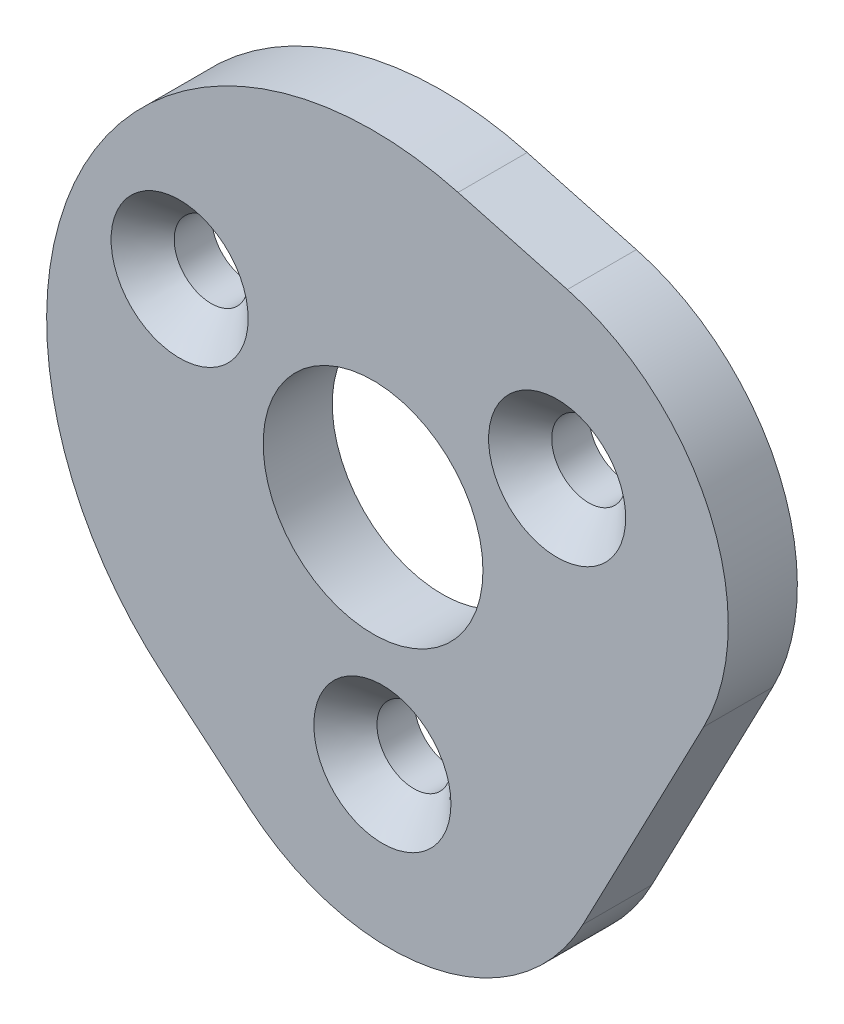
SolidWorks part; units mm, degrees
material "6061-T6 (SS)"
ref_plane "Front Plane" through (0, 0, 0) normal (0, 0, 1) x (1, 0, 0)
ref_plane "Top Plane" through (0, 0, 0) normal (0, 1, 0) x (1, 0, 0)
ref_plane "Right Plane" through (0, 0, 0) normal (1, 0, 0) x (0, 0, -1)
sketch "Sketch1" plane through (0, 0, 0) normal (0, 0, 1) x (1, 0, 0)
  line L0 (-107.4168, -1.9907) -> (-93.8964, -13.3356)
  line L2 (-76.828, 19.386) -> (-93.8964, -13.3356)
  line L3 (-85.3622, 3.0252) -> (-97.775, 9.5) construction
  line L6 (-107.4168, -1.9907) -> (-103.1456, -5.5747)
  line L7 (-83.9149, -16) -> (69.2267, -16)
  line L8 (69.2267, -16) -> (77.4756, -11.2375)
  line L9 (77.4756, -11.2375) -> (61.75, 16)
  line L10 (61.75, 16) -> (-64.275, 16)
  line L11 (-64.275, 16) -> (-72.5616, 18.2352)
  line L12 (-107.4168, -1.9907) -> (-103.1456, -5.5747) construction
  line L17 (-64.275, 16) -> (-72.5616, 18.2352) construction
  line L166 (-125.275, -23) -> (-103.8037, -23)
  line L167 (-125.275, -23) -> (-103.8037, -23)
  line L168 (-99.1549, -21.9694) -> (-88.5637, -17.0306)
  line L169 (-99.1549, -21.9694) -> (-88.5637, -17.0306)
  line L170 (-103.5739, -10.4709) -> (-125.275, -23)
  line L171 (-103.5739, -10.4709) -> (-125.275, -23)
  line L339 (-91.6684, 23.3889) -> (-93.8686, 23.9824)
  line L340 (-91.6684, 23.3889) -> (-93.8686, 23.9824)
  line L351 (-76.828, 19.386) -> (-91.6684, 23.3889)
  circle A0 centre (-97.775, 9.5) radius 5 construction
  circle A1 centre (-97.775, 9.5) radius 5 construction
  arc A2 (-103.8037, -23) -> (-99.1549, -21.9694) centre (-103.8037, -12) ccw
  arc A3 (-93.8686, 23.9824) -> (-107.4168, -1.9907) centre (-97.775, 9.5) ccw
  arc A5 (-93.8686, 23.9824) -> (-107.4168, -1.9907) centre (-97.775, 9.5) ccw
  circle A6 centre (-97.775, 9.5) radius 5.05
  arc A59 (-103.8037, -23) -> (-99.1549, -21.9694) centre (-103.8037, -12) ccw
  arc A60 (-83.9149, -16) -> (-88.5637, -17.0306) centre (-83.9149, -27) ccw
  arc A61 (-83.9149, -16) -> (-88.5637, -17.0306) centre (-83.9149, -27) ccw
  arc A62 (-103.5739, -10.4709) -> (-103.1456, -5.5747) centre (-105.0739, -7.8728) ccw
  arc A63 (-103.5739, -10.4709) -> (-103.1456, -5.5747) centre (-105.0739, -7.8728) ccw
  arc A144 (-74.6395, 20.2232) -> (-72.5616, 18.2352) centre (-71.7803, 21.1317) ccw
  arc A146 (-74.6395, 20.2232) -> (-105.775, 43) centre (-105.775, 10.3307) ccw
  arc A148 (-88.2446, 27.7057) -> (-105.775, 43) centre (-117.312, 12.0824) ccw
  arc A150 (-91.6684, 23.3889) -> (-88.2446, 27.7057) centre (-90.8871, 26.2854) ccw
  dimension "D3" = 10.1
  dimension "D2" = 14
  dimension "D1" = 0
extrude "Boss-Extrude1" add sketch "Sketch1" along normal blind 3.175 contours A5 L0 L2 A6 region at (-110.6117, 16.1959, 0)
fillet "Fillet1" radius 10 2 edges at (-93.8964, -13.3356, 1.5875) (-76.828, 19.386, 1.5875)
sketch "Sketch2" plane through (0, 0, 3.175) normal (0, 0, 1) x (1, 0, 0)
  line L0 (-102.2525, 11.8356) -> (-111.0744, 16.4373) construction
  circle A1 centre (-97.775, 9.5) radius 5.05 construction
  arc A3 (-93.8686, 23.9824) -> (-107.4168, -1.9907) centre (-97.775, 9.5) ccw construction
  circle A4 centre (-97.775, 9.5) radius 5.05 construction
  arc A5 (-93.8686, 23.9824) -> (-107.4168, -1.9907) centre (-97.775, 9.5) ccw construction
  point P8 (-106.6634, 14.1364)
hole_wizard "CSK for M3 Flat Head Machine Screw1" positions "Sketch3" profile "Sketch4" countersink size "M3" standard "ANSI Metric" end condition through all
sketch "Sketch3" plane through (0, 0, 3.175) normal (0, 0, 1) x (1, 0, 0)
  point P0 (-106.6634, 14.1364)
  point P3 (-106.6634, 14.1364)
sketch "Sketch4" plane through (-106.6634, 14.1364, 3.175) normal (1, 0, 0) x (0, -1, 0)
  line L0 (0, 0) -> (0, 3.175)
  line L1 (0, 3.175) -> (1.7, 3.175)
  line L2 (1.7, 3.175) -> (1.7, 1.45)
  line L3 (1.7, 1.45) -> (3.15, 0)
  line L5 (3.15, 0) -> (0, 0)
  line L6 (-1.7, 1.45) -> (-3.15, 0) construction
  line L11 (0, -6.35) -> (0, 107.95) construction
  dimension "Thru Hole Dia." = 3.4
  dimension "Thru Hole Depth" = 3.175
  dimension "Near C'Sink Dia." = 6.3
  dimension "Near C'Sink Angle" = 90
pattern_circular "CirPattern1" count 3 over 360 about axis through (-97.775, 9.5, 3.175) along (0, 0, -1) of "CSK for M3 Flat Head Machine Screw1" reverse direction yes
